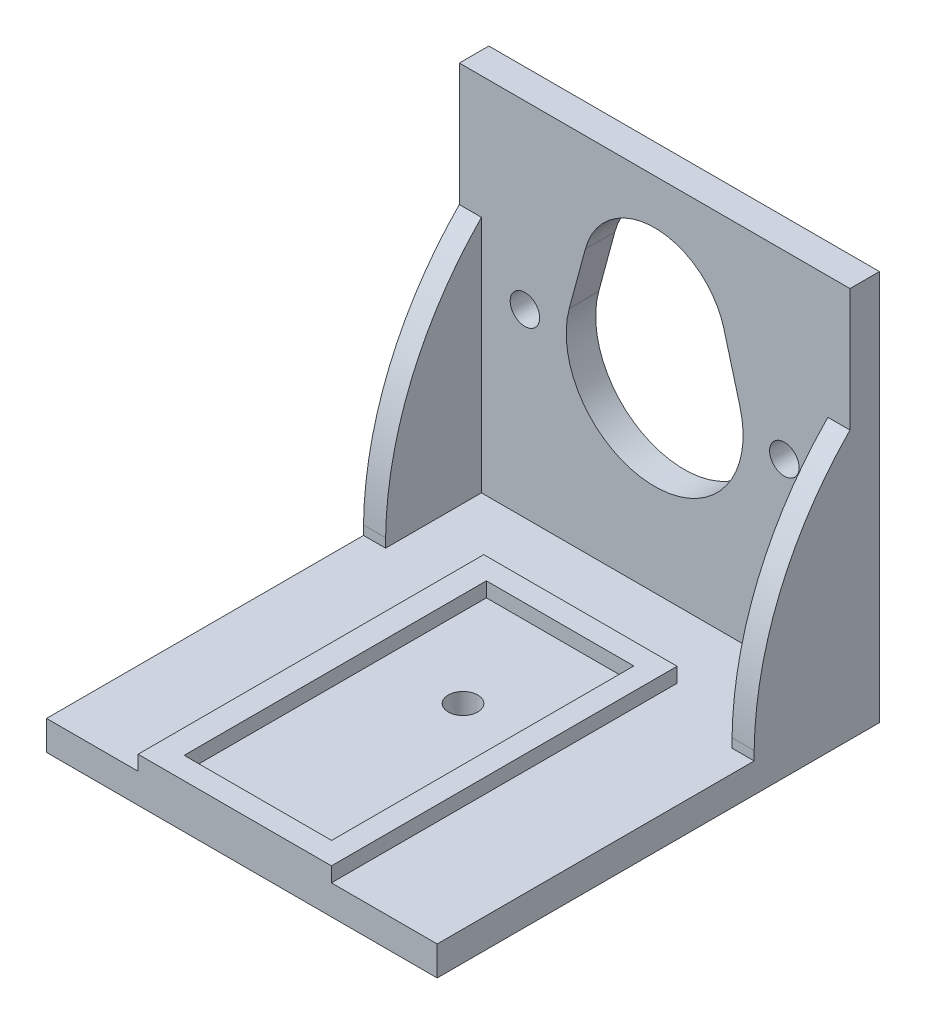
SolidWorks part; units mm, degrees
ref_plane "Plano frontal" through (0, 0, 0) normal (0, 0, 1) x (1, 0, 0)
ref_plane "Plano superior" through (0, 0, 0) normal (0, 1, 0) x (1, 0, 0)
ref_plane "Plano direito" through (0, 0, 0) normal (1, 0, 0) x (0, 0, -1)
sketch "Esboço1" plane through (0, 0, 0) normal (0, 0, 1) x (1, 0, 0)
  line L1 (0, 0) -> (53, 0)
  line L2 (0, 0) -> (0, 53)
  line L3 (0, 53) -> (53, 53)
  line L4 (53, 0) -> (53, 53)
  dimension "D1" = 53
  dimension "D2" = 53
extrude "Ressalto-extrusão1" add sketch "Esboço1" along normal blind 4
sketch "Esboço2" plane through (0, 0, 0) normal (0, 0, 1) x (1, 0, 0)
  line L0 (53, 0) -> (53, 53) construction
  line L1 (0, 0) -> (53, 0)
  line L2 (0, 0) -> (0, 4)
  line L3 (0, 4) -> (53, 4)
  line L4 (53, 0) -> (53, 4)
  dimension "D1" = 4
extrude "Ressalto-extrusão2" add sketch "Esboço2" along normal blind 60
sketch "Esboço3" plane through (0, 0, 0) normal (0, 0, 1) x (1, 0, 0)
  line L0 (26.5, 53) -> (26.5, 27.4237) construction
  line L1 (53, 53) -> (0, 53) construction
  line L2 (0, 0) -> (53, 0) construction
  line L3 (26.5, 0) -> (53, 28.5) construction
  line L4 (53, 4) -> (53, 53) construction
  line L5 (53, 28.5) -> (38.5, 28.5) construction
  line L6 (0, 53) -> (0, 4) construction
  line L7 (17.0982, 39.7046) -> (14.9158, 31.6316)
  line L8 (35.9018, 39.7046) -> (38.0842, 31.6316)
  line L10 (26.5, 16.5) -> (26.5, 0) construction
  line L11 (14.5, 28.5) -> (0, 28.5) construction
  arc A0 (14.9158, 31.6316) -> (38.0842, 31.6316) centre (26.5, 28.5) ccw
  arc A1 (35.9018, 39.7046) -> (17.0982, 39.7046) centre (26.5, 37.163) ccw
  dimension "D1" = 24
extrude "Corte-extrusão1" cut sketch "Esboço3" along direction (0, 0, -1) on the side of the normal blind 21 and the other way blind 18
sketch "Esboço4" plane through (0, 0, 0) normal (0, 0, 1) x (1, 0, 0)
  line L0 (0, 28.5) -> (53, 28.5) construction
  line L1 (0, 53) -> (0, 4) construction
  line L2 (53, 4) -> (53, 53) construction
  line L3 (26.5, 40.5) -> (26.5, 0) construction
  line L4 (0, 0) -> (53, 0) construction
  circle A0 centre (8.9, 28.5) radius 2
  circle A1 centre (44.1, 28.5) radius 2
  circle A2 centre (26.5, 28.5) radius 12 construction
  dimension "D3" = 4
  dimension "D4" = 4
  dimension "D1" = 35.2
  dimension "D2" = 17.6
extrude "Corte-extrusão2" cut sketch "Esboço4" along direction (0, 0, -1) on the side of the normal blind 17 and the other way blind 15
sketch "Esboço5" plane through (0, 0, 0) normal (0, 0, 1) x (1, 0, 0)
  line L0 (0, 53) -> (0, 4) construction
  line L1 (0, 0) -> (53, 0) construction
  line L2 (0, 36.3739) -> (3, 36.3739)
  line L3 (0, 36.3739) -> (0, 0)
  line L4 (0, 0) -> (3, 0)
  line L5 (3, 36.3739) -> (3, 0)
  line L6 (0, 36.3739) -> (53, 36.3739) construction
  line L7 (53, 4) -> (53, 53) construction
  line L9 (53, 36.3739) -> (50, 36.3739)
  line L10 (53, 36.3739) -> (53, 0)
  line L11 (53, 0) -> (50, 0)
  line L12 (50, 36.3739) -> (50, 0)
  dimension "D1" = 3
  dimension "D2" = 3
extrude "Ressalto-extrusão3" add sketch "Esboço5" along normal blind 17
sketch "Esboço6" plane through (0, 0, 0) normal (1, 0, 0) x (0, 0, -1)
  line L0 (-4, 36.3739) -> (-17, 36.3739)
  line L1 (-17, 36.3739) -> (-17, 4)
  arc A0 (-17, 4) -> (-4, 36.3739) centre (28.283, 4.6133) cw
extrude "Corte-extrusão3" cut sketch "Esboço6" along direction (1, 0, 0) on the side of the normal blind 62 and the other way blind 15 contours L1 A0 L0 region at (0, 28.6879, 13.2183)
sketch "Esboço7" plane through (0, 0, 0) normal (0, 1, 0) x (1, 0, 0)
  line L0 (26.5, 0) -> (26.5, -60) construction
  line L1 (53, 0) -> (0, 0) construction
  line L2 (53, -60) -> (0, -60) construction
  line L4 (15.6741, -57) -> (35.6741, -57)
  line L5 (15.6741, -57) -> (15.6741, -16)
  line L6 (15.6741, -16) -> (35.6741, -16)
  line L7 (35.6741, -57) -> (35.6741, -16)
  line L8 (12.4175, -60) -> (38.6461, -60)
  line L9 (12.4175, -60) -> (12.4175, -13.1011)
  line L10 (12.4175, -13.1011) -> (38.6461, -13.1011)
  line L11 (38.6461, -60) -> (38.6461, -13.1011)
  circle A0 centre (26.5, -30) radius 2
  dimension "D1" = 4
  dimension "D2" = 20
  dimension "D3" = 41
  dimension "D4" = 12
extrude "Ressalto-extrusão4" add sketch "Esboço7" along direction (0, -1, 0) on the side of the normal blind 6 contours L9 L10 L11 L8 | L5 L6 L7 L4
sketch "Esboço8" plane through (0, 0, 0) normal (0, 1, 0) x (1, 0, 0)
  line L0 (26.5, 0) -> (26.5, -60) construction
  line L1 (53, 0) -> (0, 0) construction
  line L2 (12.4175, -60) -> (38.6461, -60) construction
  circle A0 centre (26.5, -30) radius 2
  dimension "D1" = 4
extrude "Corte-extrusão4" cut sketch "Esboço8" along direction (0, -1, 0) on the side of the normal blind 10 and the other way blind 21
